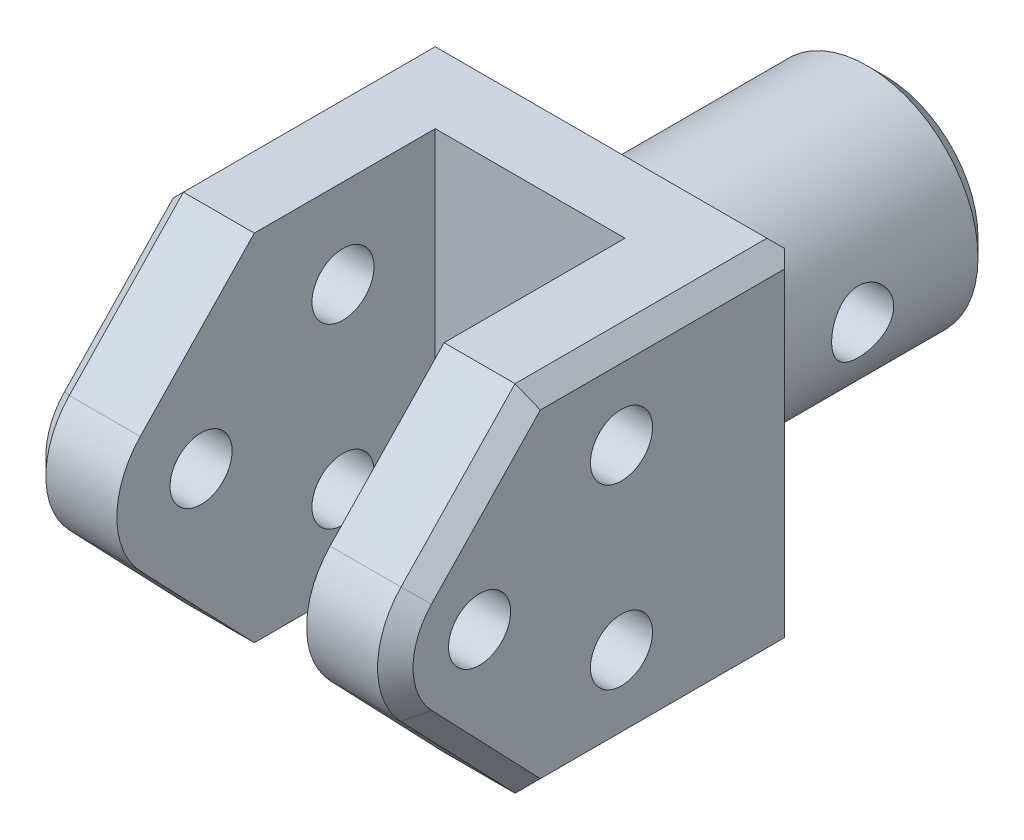
SolidWorks part; units mm, degrees
ref_plane "正面(Front)" through (0, 0, 0) normal (0, 0, 1) x (1, 0, 0)
ref_plane "平面(Top)" through (0, 0, 0) normal (0, 1, 0) x (1, 0, 0)
ref_plane "右側面(Right)" through (0, 0, 0) normal (1, 0, 0) x (0, 0, -1)
sketch "ｽｹｯﾁ1" plane through (0, 0, 0) normal (0, 0, 1) x (1, 0, 0)
  circle A0 centre (0, 0) radius 6.25
  dimension "D1" = 12.5
extrude "ﾎﾞｽ - 押し出し1" add sketch "ｽｹｯﾁ1" against normal blind 15
sketch "ｽｹｯﾁ2" plane through (0, 0, 0) normal (0, 0, 1) x (1, 0, 0)
  line L1 (-10.35, 10) -> (10.35, 10)
  line L2 (-10.35, 10) -> (-10.35, -10)
  line L3 (-10.35, -10) -> (10.35, -10)
  line L4 (10.35, 10) -> (10.35, -10)
  line L5 (-10.35, 10) -> (10.35, -10) construction
  line L6 (-10.35, -10) -> (10.35, 10) construction
  point P0 (0, 0)
  dimension "D1" = 20.7
  dimension "D2" = 20
extrude "ﾎﾞｽ - 押し出し2" add sketch "ｽｹｯﾁ2" along normal blind 5
sketch "ｽｹｯﾁ3" plane through (0, 0, 5) normal (0, 0, 1) x (1, 0, 0)
  line L0 (-10.35, -10) -> (10.35, -10) construction
  line L1 (10.35, 10) -> (5.35, 10)
  line L2 (10.35, 10) -> (10.35, -10)
  line L3 (10.35, -10) -> (5.35, -10)
  line L4 (5.35, 10) -> (5.35, -10)
  line L6 (-10.35, 10) -> (-5.35, 10)
  line L7 (-10.35, 10) -> (-10.35, -10)
  line L8 (-10.35, -10) -> (-5.35, -10)
  line L9 (-5.35, 10) -> (-5.35, -10)
  dimension "D1" = 5
extrude "ﾎﾞｽ - 押し出し3" add sketch "ｽｹｯﾁ3" along normal blind 10.2
fillet "ﾌｨﾚｯﾄ1" [suppressed] radius 5
sketch "ｽｹｯﾁ4" plane through (0, 0, 0) normal (1, 0, 0) x (0, 0, -1)
  line L0 (0, 0) -> (-25.6063, 0) construction
  line L2 (-15.2, -10) -> (-15.2, 10) construction
  circle A0 centre (-10.2, 5) radius 1.75
  circle A1 centre (-10.2, -5) radius 1.75
  dimension "D1" = 3.5
  dimension "D2" = 5
  dimension "D3" = 5
extrude "ｶｯﾄ - 押し出し1" cut sketch "ｽｹｯﾁ4" against normal through all both and the other way through all
sketch "ｽｹｯﾁ5" plane through (0, 0, 0) normal (1, 0, 0) x (0, 0, -1)
  line L0 (0, 0) -> (17.4374, 0) construction
  line L1 (0, -10) -> (0, 10) construction
  circle A0 centre (7.5, 0) radius 1.75
  dimension "D1" = 7.5
  dimension "D2" = 3.5
extrude "ｶｯﾄ - 押し出し2" cut sketch "ｽｹｯﾁ5" against normal through all both and the other way through all
sketch "ｽｹｯﾁ6" plane through (-10.35, 0, 0) normal (-1, 0, 0) x (0, 0, 1)
  line L0 (15.2, 10) -> (21.6305, 3.2854)
  line L1 (0, 0) -> (33.6489, 0) construction
  line L2 (15.2, -10) -> (21.6305, -3.2854)
  line L3 (15.2, -10) -> (15.2, 10)
  arc A0 (21.6305, 3.2854) -> (21.6305, -3.2854) centre (18.2, 0) cw
  circle A1 centre (18.2, 0) radius 1.75
  circle A2 centre (10.2, 5) radius 1.75 construction
  dimension "D1" = 3.5
  dimension "D2" = 8
  dimension "D3" = 3
extrude "ﾎﾞｽ - 押し出し4" add sketch "ｽｹｯﾁ6" against normal blind 5
fillet "ﾌｨﾚｯﾄ2" [suppressed] radius 10
mirror "ﾐﾗｰ1" about plane through (0, 0, 0) normal (1, 0, 0) of "ﾎﾞｽ - 押し出し4", "ﾌｨﾚｯﾄ2"
chamfer "面取り1" distance 1 angle 45 4 edges at (0, 10, 0) (-10.35, 0, 0) (0, -10, 0) (10.35, 0, 0)
chamfer "面取り2" distance 1 angle 45 10 edges at (10.35, 10, 8.1) (10.35, -10, 8.1) (-10.35, 10, 8.1) (-10.35, -10, 8.1) (10.35, 6.6427, 18.4153) (10.35, 0, 22.95) (10.35, -6.6427, 18.4153) (-10.35, 6.6427, 18.4153) (-10.35, 0, 22.95) (-10.35, -6.6427, 18.4153)
chamfer "面取り3" distance 1 angle 45 1 edges at (6.25, 0, -15)
